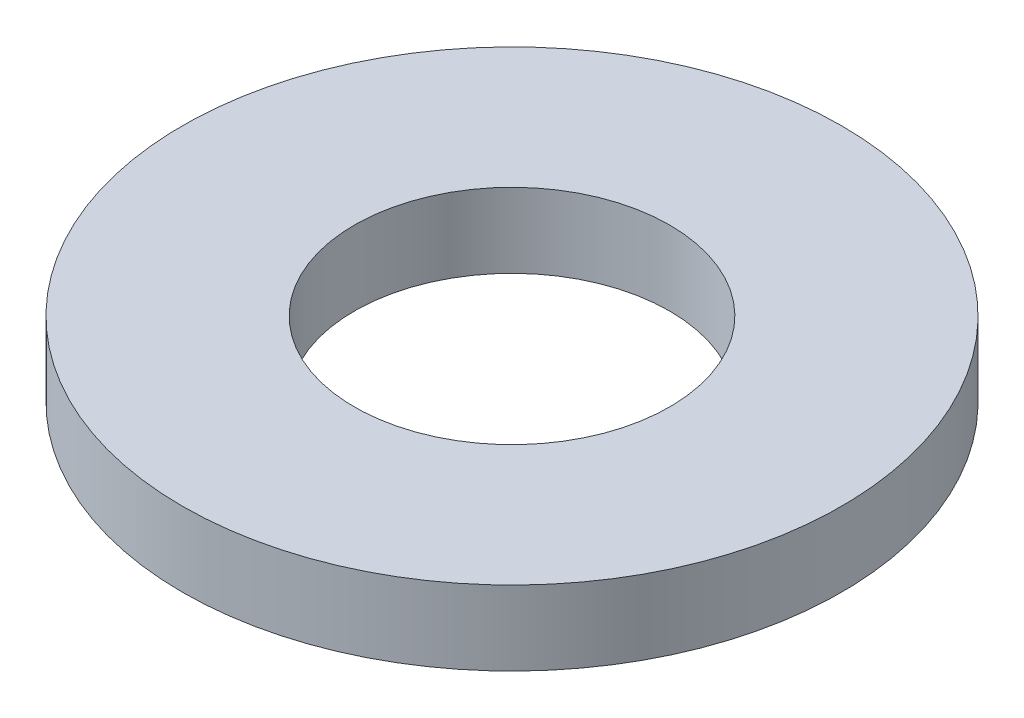
SolidWorks part; units mm, degrees
ref_plane "Front Plane" through (0, 0, 0) normal (0, 0, 1) x (1, 0, 0)
ref_plane "Top Plane" through (0, 0, 0) normal (0, 1, 0) x (1, 0, 0)
ref_plane "Right Plane" through (0, 0, 0) normal (1, 0, 0) x (0, 0, -1)
sketch "Sketch1" plane through (0, 0, 0) normal (0, 1, 0) x (1, 0, 0)
  circle A0 centre (0, 0) radius 57.5
  dimension "FLANGE_OD" = 115
extrude "Boss-Extrude1" add sketch "Sketch1" along normal blind 13
sketch "Sketch2" plane through (0, 0, 0) normal (0, 1, 0) x (1, 0, 0)
  circle A0 centre (0, 0) radius 27.5
  dimension "BORE_D" = 55
extrude "Cut-Extrude1" cut sketch "Sketch2" along normal through all
sketch "Sketch3" plane through (0, 13, 0) normal (0, 1, 0) x (1, 0, 0)
  circle A0 centre (0, 0) radius 16.9805 construction
  circle A1 centre (-16.9805, 0) radius 1.5578
  dimension "BOLT_D" = 3.1155
  dimension "BOLT_PCD" = 33.961
extrude "Cut-Extrude2" cut sketch "Sketch3" against normal blind 12.8808 rebuild error yes
pattern_circular "CirPattern1" count 4 over 360 rebuild error yes
